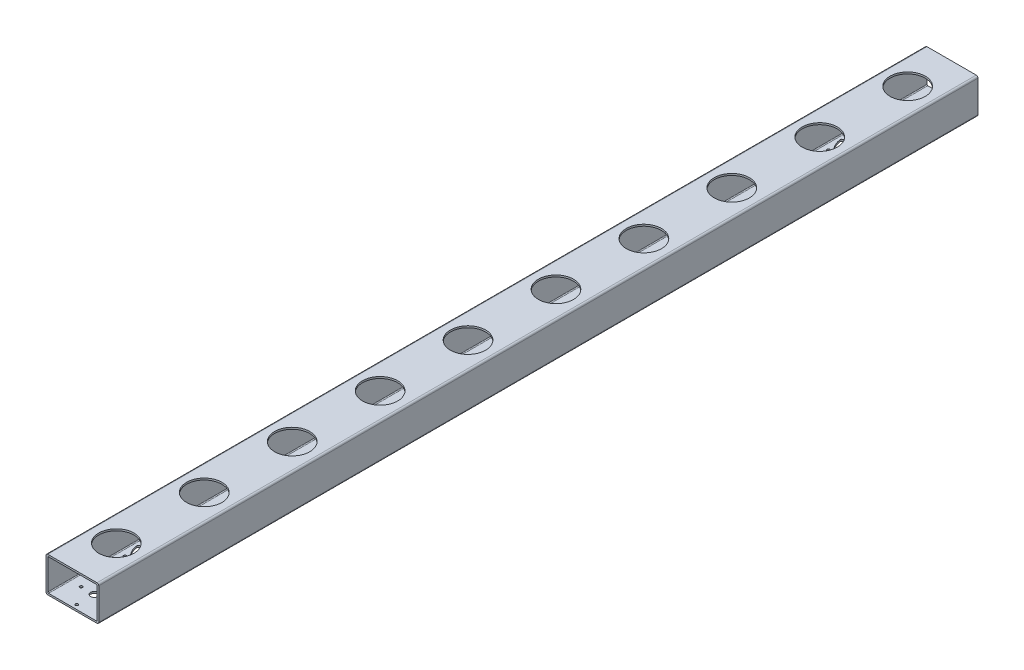
SolidWorks part; units mm, degrees
ref_plane "Plan de face" through (0, 0, 0) normal (0, 0, 1) x (1, 0, 0)
ref_plane "Plan de dessus" through (0, 0, 0) normal (0, 1, 0) x (1, 0, 0)
ref_plane "Plan de droite" through (0, 0, 0) normal (1, 0, 0) x (0, 0, -1)
sketch "Esquisse1" plane through (0, 0, 0) normal (0, 0, 1) x (1, 0, 0)
  line L0 (2, 2) -> (58, 2)
  line L1 (0, 0) -> (60, 0)
  line L2 (0, 0) -> (0, 40)
  line L3 (0, 40) -> (60, 40)
  line L4 (60, 0) -> (60, 40)
  line L5 (58, 2) -> (58, 38)
  line L6 (2, 38) -> (58, 38)
  line L7 (2, 2) -> (2, 38)
  dimension "D1" = 60
  dimension "D2" = 40
  dimension "D3" = 2
extrude "Boss.-Extru.1" add sketch "Esquisse1" along normal blind 1000
fillet "Congé1" radius 1 4 edges at (58, 2, 500) (58, 38, 500) (2, 38, 500) (2, 2, 500)
fillet "Congé2" radius 2 4 edges at (60, 0, 500) (0, 0, 500) (60, 40, 500) (0, 40, 500)
sketch "Esquisse2" plane through (0, 40, 0) normal (0, 1, 0) x (1, 0, 0)
  line L0 (30, 0) -> (30, -50) construction
  line L1 (58, 0) -> (2, 0) construction
  circle A0 centre (30, -50) radius 20
  circle A1 centre (30, -150) radius 20
  circle A2 centre (30, -250) radius 20
  circle A3 centre (30, -350) radius 20
  circle A4 centre (30, -450) radius 20
  circle A5 centre (30, -550) radius 20
  circle A6 centre (30, -650) radius 20
  circle A7 centre (30, -750) radius 20
  circle A8 centre (30, -850) radius 20
  circle A9 centre (30, -950) radius 20
  dimension "D1" = 40
  dimension "D2" = 50
  dimension "D4" = 100
  dimension "D3" = 10
extrude "Enlèv. mat.-Extru.1" cut sketch "Esquisse2" against normal up to next
sketch "Esquisse3" plane through (0, 0, 0) normal (0, -1, 0) x (1, 0, 0)
  line L0 (30, 975) -> (30, 1000) construction
  line L1 (2, 1000) -> (58, 1000) construction
  line L2 (30, 25) -> (30, 0) construction
  line L3 (2, 0) -> (58, 0) construction
  line L4 (30, 975) -> (30, 25) construction
  circle A0 centre (30, 975) radius 4.25
  circle A1 centre (30, 25) radius 4.25
  circle A2 centre (30, 500) radius 4.25
  dimension "D2" = 8.5
  dimension "D1" = 25
extrude "Enlèv. mat.-Extru.2" cut sketch "Esquisse3" against normal up to next
sketch "Esquisse4" plane through (0, 40, 0) normal (0, 1, 0) x (1, 0, 0)
  line L0 (12.3223, -32.3223) -> (47.6777, -67.6777) construction
  line L1 (2, 0) -> (2, -1000) construction
  circle A0 centre (30, -50) radius 25 construction
  circle A1 centre (30, -50) radius 20 construction
  circle A2 centre (12.3223, -32.3223) radius 1.6
  circle A3 centre (47.6777, -67.6777) radius 1.6
  point P6 (30, -50)
  dimension "D1" = 50
  dimension "D3" = 3.2
  dimension "D2" = 45
extrude "Enlèv. mat.-Extru.3" [suppressed] cut sketch "Esquisse4" against normal up to next
sketch "Esquisse6" plane through (0, 0, 0) normal (0, -1, 0) x (-1, 0, 0)
  line L0 (-20, -400) -> (-40, -400) construction
  line L1 (0, -400) -> (-20, -400) construction
  line L3 (0, 0) -> (0, -1000) construction
  line L4 (-40, -400) -> (-60, -400) construction
  line L5 (-60, -1000) -> (-60, 0) construction
  line L6 (-30, -370) -> (-30, -400) construction
  line L7 (-30, -400) -> (-30, -430) construction
  circle A0 centre (-20, -400) radius 2.25
  circle A1 centre (-40, -400) radius 2.25
  circle A2 centre (-30, -350) radius 20 construction
  circle A3 centre (-30, -450) radius 20 construction
  dimension "D2" = 4.5
  dimension "D1" = 20
extrude "Enlèv. mat.-Extru.4" cut sketch "Esquisse6" against normal up to next
pattern_linear "Répétition linéaire1" count 3 spacing 200 along (0, 0, 1) count 2 spacing 200 along (0, 0, -1) of "Enlèv. mat.-Extru.4"
sketch "Esquisse7" plane through (0, 0, 0) normal (0, -1, 0) x (-1, 0, 0)
  line L0 (-15, -500) -> (-45, -500) construction
  line L1 (-15, -975) -> (-45, -975) construction
  line L2 (-15, -25) -> (-45, -25) construction
  circle A0 centre (-15, -25) radius 1.6
  circle A1 centre (-45, -25) radius 1.6
  circle A2 centre (-15, -500) radius 1.6
  circle A3 centre (-45, -500) radius 1.6
  circle A4 centre (-15, -975) radius 1.6
  circle A5 centre (-45, -975) radius 1.6
  point P2 (-30, -500)
  point P3 (-30, -975)
  point P7 (-30, -25)
  dimension "D1" = 3.2
  dimension "D2" = 30
extrude "Enlèv. mat.-Extru.5" cut sketch "Esquisse7" against normal up to next
pattern_linear "Répétition linéaire2" [suppressed] count 10 spacing 100 of bodies 107
sketch "Esquisse8" plane through (0, 0, 0) normal (0, -1, 0) x (-1, 0, 0)
  circle A0 centre (-38, -55.1826) radius 1.4
  circle A1 centre (-22, -55.1826) radius 1.4
  circle A2 centre (-22, -55.1826) radius 1.25 construction
  circle A3 centre (-38, -55.1826) radius 1.25 construction
  dimension "D1" = 2.8
sketch "Esquisse9" plane through (0, 0, 0) normal (0, -1, 0) x (1, 0, 0)
  circle A1 centre (30, 950) radius 9.5306 construction
  circle A2 centre (30, 950) radius 20 construction
  circle A3 centre (22, 955.18) radius 1.1
  circle A4 centre (38, 955.18) radius 1.1
  dimension "D1" = 2.2
  dimension "D2" = 5.18
  dimension "D3" = 16
extrude "Enlèv. mat.-Extru.6" cut sketch "Esquisse9" against normal up to next
pattern_linear "Répétition linéaire3" count 10 spacing 100 along (0, 0, -1) of "Enlèv. mat.-Extru.6"
sketch "Esquisse10" plane through (0, 0, 0) normal (0, -1, 0) x (1, 0, 0)
  line L0 (2, 0) -> (58, 0) construction
  line L1 (10, 80) -> (50, 80) construction
  line L2 (10, 80) -> (10, 120) construction
  line L3 (10, 120) -> (50, 120) construction
  line L4 (50, 80) -> (50, 120) construction
  line L6 (0, 100) -> (10, 100) construction
  line L7 (0, 0) -> (0, 1000) construction
  line L8 (50, 100) -> (60, 100) construction
  line L9 (60, 1000) -> (60, 0) construction
  circle A0 centre (10, 120) radius 1.75
  circle A1 centre (50, 120) radius 1.75
  circle A2 centre (50, 80) radius 1.75
  circle A3 centre (10, 80) radius 1.75
  dimension "D2" = 3.5
  dimension "D1" = 40
  dimension "D3" = 100
extrude "Enlèv. mat.-Extru.7" cut sketch "Esquisse10" against normal up to next
pattern_linear "Répétition linéaire4" count 2 spacing 800 along (0, 0, 1) of "Enlèv. mat.-Extru.7"
sketch "Esquisse11" plane through (0, 0, 0) normal (0, -1, 0) x (1, 0, 0)
  line L1 (30, 910) -> (30, 916) construction
  line L2 (30, 918) -> (30, 924) construction
  line L3 (12.0278, 899) -> (6.0208, 899)
  line L4 (20.0501, 899) -> (14.0313, 899)
  line L6 (20.0501, 901) -> (14.0313, 901)
  line L8 (12.0278, 901) -> (6.0208, 901)
  line L9 (20.0501, 901) -> (20.0501, 899) construction
  line L10 (38.1201, 916.0644) -> (41.1236, 921.2666)
  line L11 (39.8521, 915.0644) -> (42.8556, 920.2666)
  line L12 (35.841, 908.1168) -> (38.8504, 913.3293)
  line L13 (34.1089, 909.1168) -> (37.1183, 914.3293)
  line L14 (39.8521, 884.9356) -> (42.8556, 879.7334)
  line L15 (38.1201, 883.9356) -> (41.1236, 878.7334)
  line L16 (34.1089, 890.8832) -> (37.1183, 885.6707)
  line L17 (35.841, 891.8832) -> (38.8504, 886.6707)
  arc A0 (41.1236, 921.2666) -> (42.8556, 920.2666) centre (30, 900) ccw
  arc A1 (20.0501, 899) -> (34.1089, 890.8832) centre (30, 900) ccw
  arc A2 (14.0313, 899) -> (37.1183, 885.6707) centre (30, 900) ccw
  arc A3 (12.0278, 899) -> (38.1201, 883.9356) centre (30, 900) ccw
  arc A4 (24.1103, 908.0815) -> (20.0094, 900.434) centre (30, 900) ccw construction
  arc A5 (39.8521, 884.9356) -> (39.8521, 915.0644) centre (30, 900) ccw
  arc A6 (38.8504, 886.6707) -> (38.8504, 913.3293) centre (30, 900) ccw
  arc A7 (35.841, 891.8832) -> (35.841, 908.1168) centre (30, 900) ccw
  arc A8 (38.1201, 916.0644) -> (12.0278, 901) centre (30, 900) ccw
  arc A9 (37.1183, 914.3293) -> (14.0313, 901) centre (30, 900) ccw
  arc A10 (34.1089, 909.1168) -> (20.0501, 901) centre (30, 900) ccw
  dimension "D1" = 48
  dimension "D2" = 20
  dimension "D3" = 2
  dimension "D4" = 2
  dimension "D5" = 3
extrude "Enlèv. mat.-Extru.8" cut sketch "Esquisse11" against normal up to next contours A8 L10 A0 L8 | A3 L3 A0 L15 | A5 L14 A0 L11 | L4 A2 L16 A1 | A7 L17 A6 L12 | A10 L13 A9 L6 region at (20.7902, 0, 884.0481) region at (41.7257, 0, 882.5492) region at (18.2098, 0, 920.4212) region at (24.3698, 0, 890.2482) region at (24.3698, 0, 909.7518) region at (41.2604, 0, 900)
fillet "Congé3" radius 2 24 edges at (6.0208, 1, 899) (12.0278, 1, 899) (14.0313, 1, 899) (20.0501, 1, 899) (34.1089, 1, 890.8832) (37.1183, 1, 885.6707) (38.1201, 1, 883.9356) (41.1236, 1, 878.7334) (42.8556, 1, 879.7334) (38.8504, 1, 886.6707) (39.8521, 1, 884.9356) (35.841, 1, 891.8832) (39.8521, 1, 915.0644) (42.8556, 1, 920.2666) (35.841, 1, 908.1168) (38.8504, 1, 913.3293) (34.1089, 1, 909.1168) (37.1183, 1, 914.3293) (20.0501, 1, 901) (14.0313, 1, 901) (6.0208, 1, 901) (12.0278, 1, 901) (38.1201, 1, 916.0644) (41.1236, 1, 921.2666)
pattern_linear "Répétition linéaire5" count 2 spacing 800 along (0, 0, -1) of "Enlèv. mat.-Extru.8", "Congé3"
sketch "Esquisse12" plane through (0, 0, 0) normal (0, -1, 0) x (1, 0, 0)
  line L0 (38, 755.18) -> (38, 740.18) construction
  line L1 (10, 740.18) -> (50, 740.18) construction
  line L2 (10, 740.18) -> (10, 670.18) construction
  line L3 (10, 670.18) -> (50, 670.18) construction
  line L4 (50, 740.18) -> (50, 670.18) construction
  line L5 (22, 655.18) -> (22, 670.18) construction
  line L6 (10, 705.18) -> (0, 705.18) construction
  line L7 (50, 705.18) -> (60, 705.18) construction
  line L8 (60, 1000) -> (60, 0) construction
  line L9 (0, 0) -> (0, 1000) construction
  circle A0 centre (10, 740.18) radius 1.6
  circle A1 centre (50, 740.18) radius 1.6
  circle A2 centre (50, 670.18) radius 1.6
  circle A3 centre (10, 670.18) radius 1.6
  dimension "D1" = 3.2
  dimension "D2" = 40
  dimension "D3" = 70
extrude "Enlèv. mat.-Extru.9" cut sketch "Esquisse12" against normal up to next
sketch "Esquisse13" plane through (0, 0, 0) normal (0, -1, 0) x (1, 0, 0)
  line L0 (17, 722.18) -> (0, 722.18) construction
  line L1 (17, 729.18) -> (43, 729.18)
  line L2 (17, 729.18) -> (17, 715.18)
  line L3 (17, 715.18) -> (43, 715.18)
  line L4 (43, 729.18) -> (43, 715.18)
  line L5 (0, 0) -> (0, 1000) construction
  line L6 (43, 722.18) -> (60, 722.18) construction
  line L7 (60, 1000) -> (60, 0) construction
  line L9 (30, 705.18) -> (30, 715.18) construction
  line L10 (17, 705.18) -> (30, 705.18) construction
  line L11 (30, 705.18) -> (43, 705.18) construction
  circle A0 centre (17, 705.18) radius 1.9
  circle A1 centre (30, 705.18) radius 1.9
  circle A2 centre (43, 705.18) radius 1.9
  circle A3 centre (10, 740.18) radius 1.6 construction
  dimension "D6" = 3.8
  dimension "D3" = 18
  dimension "D1" = 26
  dimension "D2" = 14
  dimension "D4" = 13
  dimension "D5" = 10
extrude "Enlèv. mat.-Extru.10" cut sketch "Esquisse13" against normal up to next
sketch "Esquisse14" plane through (0, 0, 0) normal (0, -1, 0) x (1, 0, 0)
  line L0 (30, 995) -> (30, 1000) construction
  line L1 (2, 1000) -> (58, 1000) construction
  line L2 (30, 5) -> (30, 0) construction
  line L3 (2, 0) -> (58, 0) construction
  circle A0 centre (30, 5) radius 1.6
  circle A1 centre (30, 995) radius 1.6
  dimension "D1" = 3.2
  dimension "D2" = 5
extrude "Enlèv. mat.-Extru.11" cut sketch "Esquisse14" against normal up to next
sketch "Esquisse15" plane through (0, 0, 0) normal (0, -1, 0) x (1, 0, 0)
  line L4 (20, 400) -> (40, 400) construction
  line L5 (30, 425) -> (30, 400) construction
  circle A3 centre (30, 425) radius 2.5
  dimension "D3" = 5
  dimension "D4" = 25
extrude "Enlèv. mat.-Extru.12" cut sketch "Esquisse15" against normal up to next
sketch "Esquisse16" plane through (0, 0, 0) normal (0, -1, 0) x (1, 0, 0)
  line L0 (30, 962.7) -> (30, 950) construction
  line L1 (30, 950) -> (30, 937.3) construction
  line L2 (22, 955.18) -> (30, 955.18) construction
  line L3 (30, 955.18) -> (38, 955.18) construction
  circle A0 centre (30, 962.7) radius 1.65
  circle A1 centre (30, 937.3) radius 1.65
  circle A2 centre (38, 955.18) radius 1.1 construction
  point P5 (30, 950)
  dimension "D1" = 3.3
  dimension "D2" = 5.18
  dimension "D3" = 25.4
extrude "Enlèv. mat.-Extru.13" cut sketch "Esquisse16" against normal up to next
pattern_linear "Répétition linéaire6" count 10 spacing 100 along (0, 0, -1) of "Enlèv. mat.-Extru.13"
